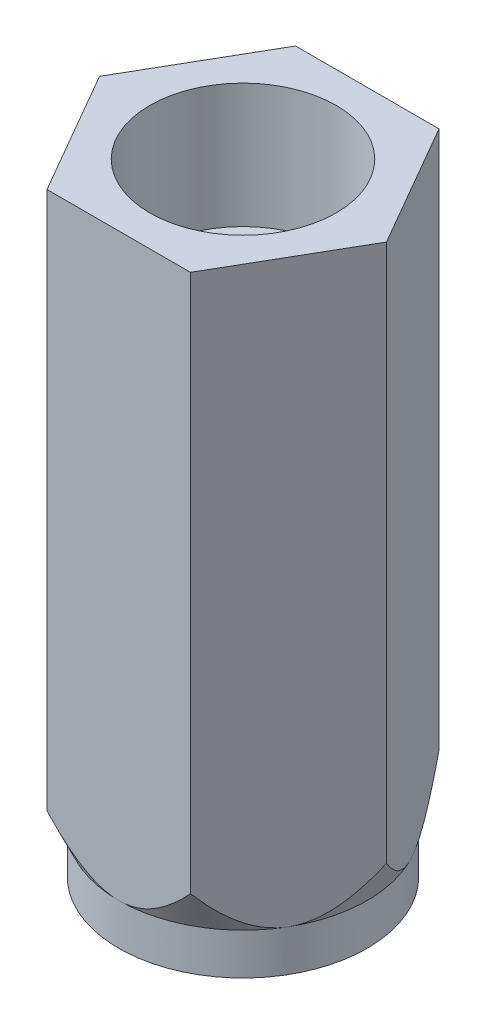
SolidWorks part; units mm, degrees
ref_plane "Front Plane" through (0, 0, 0) normal (0, 0, 1) x (1, 0, 0)
ref_plane "Top Plane" through (0, 0, 0) normal (0, 1, 0) x (1, 0, 0)
ref_plane "Right Plane" through (0, 0, 0) normal (1, 0, 0) x (0, 0, -1)
sketch "Sketch1" plane through (0, 0, 0) normal (0, 1, 0) x (1, 0, 0)
  circle A0 centre (0, 0) radius 2.5
  circle A1 centre (0, 0) radius 1.7
  dimension "D1" = 5
  dimension "D2" = 3.4
extrude "Boss-Extrude1" add sketch "Sketch1" along normal blind 2
sketch "Sketch2" plane through (0, 0, 0) normal (0, -1, 0) x (1, 0, 0)
  circle A0 centre (0, 0) radius 3
  circle A1 centre (0, 0) radius 2.25
  dimension "D1" = 6
  dimension "D2" = 4.5
extrude "Boss-Extrude2" add sketch "Sketch2" against normal blind 15
sketch "Sketch4" plane through (0, 2, 0) normal (0, 1, 0) x (1, 0, 0)
  line L1 (0, 0) -> (-2.25, 0)
  line L2 (0, 0) -> (2.25, 0)
  circle A0 centre (0, 0) radius 2.25 construction
  circle A1 centre (0, 0) radius 2.25 construction
  circle A3 centre (0, 0) radius 2.25
  arc A4 (2.25, 0) -> (-2.25, 0) centre (0, 0) ccw
  circle A5 centre (0, 0) radius 1.7
  arc A6 (1.7, 0) -> (-1.7, 0) centre (0, 0) ccw
  circle M2 centre (0, 0) radius 1.7
  circle M3 centre (0, 0) radius 2.25
  dimension "D1" = 0
  dimension "D2" = 0
extrude "Boss-Extrude3" add sketch "Sketch4" along normal blind 10 contours L2 L1 M2 M3 region at (-1.975, 2, -0.0503)
sketch "Sketch5" plane through (0, 15, 0) normal (0, 1, 0) x (1, 0, 0)
  line L1 (1.7321, -3) -> (3.4641, 0)
  line L2 (3.4641, 0) -> (1.7321, 3)
  line L3 (1.7321, 3) -> (-1.7321, 3)
  line L4 (-1.7321, 3) -> (-3.4641, 0)
  line L5 (-3.4641, 0) -> (-1.7321, -3)
  line L6 (-1.7321, -3) -> (1.7321, -3)
  circle A0 centre (0, 0) radius 3 construction
  circle A1 centre (0, 0) radius 3 construction
  circle A3 centre (0, 0) radius 3
  circle A4 centre (0, 0) radius 3
  point P11 (0, 0)
  circle M8 centre (0, 0) radius 3
  dimension "D1" = 0
extrude "Boss-Extrude4" add sketch "Sketch5" against normal blind 13 contours L1 L2 M8 | L2 L3 M8 | L6 L1 M8 | L5 L6 M8 | L3 L4 M8 | L4 L5 M8 region at (1.5503, 15, 2.6853) region at (3.1007, 15, 0) region at (-1.5503, 15, 2.6853) region at (-3.1007, 15, 0) region at (1.5503, 15, -2.6853) region at (-1.5503, 15, -2.6853)
chamfer "Chamfer1" distance 1 distance2 0.46 6 edges at (-1.5, 2, -2.5981) (-3, 2, 0) (-1.5, 2, 2.5981) (1.5, 2, 2.5981) (3, 2, 0) (1.5, 2, -2.5981) first distance on face at (0, 0, -3)
sketch "Sketch3" plane through (0, 0, 0) normal (0, 0, 1) x (1, 0, 0)
  line L0 (0, 0) -> (0, 4.5) construction
  circle A0 centre (0, 4.5) radius 0.5
  dimension "D2" = 1
  dimension "D1" = 4.5
extrude "Cut-Extrude1" cut sketch "Sketch3" against normal through all
